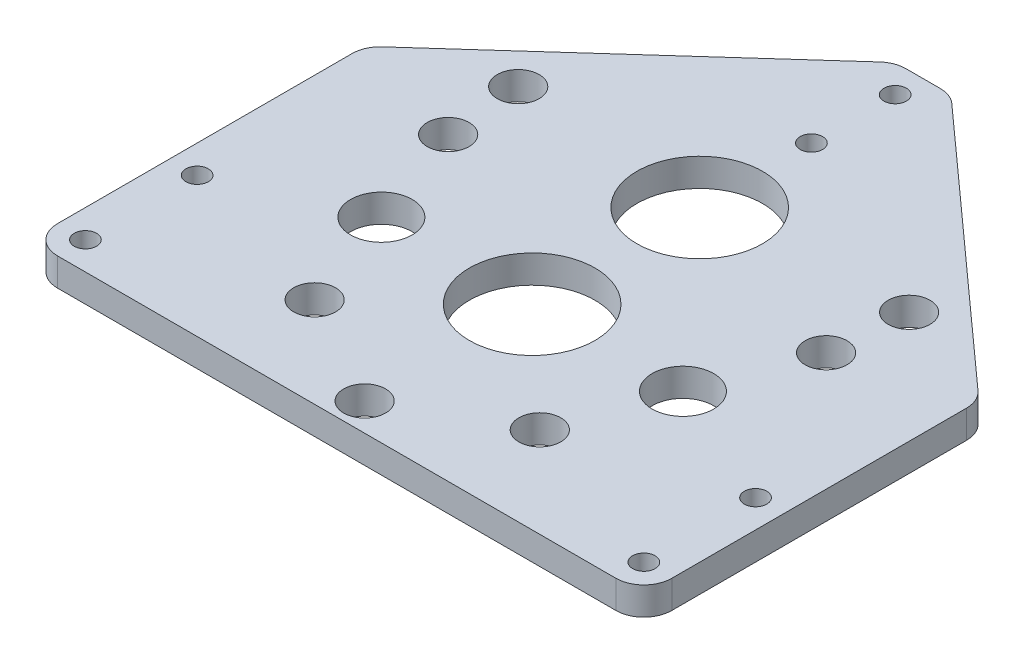
SolidWorks part; units mm, degrees
material "6061-T6 (SS)"
ref_plane "Front Plane" through (0, 0, 0) normal (0, 0, 1) x (1, 0, 0)
ref_plane "Top Plane" through (0, 0, 0) normal (0, 1, 0) x (1, 0, 0)
ref_plane "Right Plane" through (0, 0, 0) normal (1, 0, 0) x (0, 0, -1)
sketch "Sketch1" plane through (0, 0, 0) normal (0, 1, 0) x (1, 0, 0)
  line L0 (-69.85, -19.05) -> (69.85, -19.05)
  line L1 (69.85, -19.05) -> (69.85, 57.15)
  line L2 (69.85, 57.15) -> (6.35, 114.3)
  line L3 (6.35, 114.3) -> (-6.35, 114.3)
  line L4 (-6.35, 114.3) -> (-69.85, 57.15)
  line L5 (-69.85, 57.15) -> (-69.85, -19.05)
  line L6 (0, 0) -> (0, -19.05) construction
  dimension "D1" = 139.7
  dimension "D2" = 12.7
  dimension "D3" = 114.3
  dimension "D4" = 19.05
  dimension "D5" = 57.15
extrude "Boss-Extrude1" add sketch "Sketch1" along normal blind 6.35
sketch "Sketch2" plane through (0, 6.35, 0) normal (0, 1, 0) x (1, 0, 0)
  line L0 (-34.29, 25.4) -> (0, -19.05) construction
  line L1 (-69.85, -19.05) -> (69.85, -19.05) construction
  line L2 (0, -19.05) -> (34.29, 25.4) construction
  circle A0 centre (-34.29, 25.4) radius 7
  circle A1 centre (34.29, 25.4) radius 7
  dimension "D1" = 14
  dimension "D2" = 68.58
  dimension "D3" = 25.4
extrude "Motor Bearing Holes" cut sketch "Sketch2" against normal through all
sketch "Sketch3" plane through (0, 6.35, 0) normal (0, 1, 0) x (1, 0, 0)
  line L0 (-34.29, 25.4) -> (34.29, 25.4) construction
  circle A0 centre (0, 25.4) radius 14.2875
  dimension "D1" = 28.575
extrude "Cut-Extrude1" cut sketch "Sketch3" against normal through all
sketch "Sketch4" plane through (0, 6.35, 0) normal (0, 1, 0) x (1, 0, 0)
  circle A0 centre (0, 63.5) radius 14.2875
  circle A1 centre (0, 25.4) radius 14.2875 construction
  dimension "D1" = 28.575
  dimension "D2" = 38.1
extrude "Cut-Extrude2" cut sketch "Sketch4" against normal through all
extrude "Cut-Extrude3" cut sketch "Sketch5" against normal blind 50.8
sketch "Sketch5" plane through (0, 38.1, 19.05) normal (0, 1, 0) x (-0.9584, 0, 0.2853)
  circle A0 centre (21.6972, -77.741) radius 4.7625
  circle A1 centre (18.6656, -27.0315) radius 4.7625
  circle A2 centre (-30.411, -12.4209) radius 4.7625
  circle A3 centre (-60.6842, -53.2152) radius 4.7625
hole_wizard "#10 Clearance Hole1" positions "Sketch6" profile "Sketch7" hole size "#10" standard "ANSI Inch" end condition through all
sketch "Sketch6" plane through (0, 6.35, 19.05) normal (0, 1, 0) x (1, 0, 0)
  point P0 (-63.5, 6.35)
  point P2 (63.5, 6.35)
  point P13 (0, 107.95)
sketch "Sketch7" plane through (-63.5, 6.35, 12.7) normal (1, 0, 0) x (0, 0, 1)
  line L0 (0, 0) -> (0, 6.35)
  line L1 (0, 6.35) -> (2.5527, 6.35)
  line L2 (2.5527, 6.35) -> (2.5527, 0)
  line L3 (2.5527, 0) -> (0, 0)
  line L4 (0, -6.35) -> (0, 107.95) construction
  dimension "Thru Hole Dia." = 5.1054
  dimension "Thru Hole Depth" = 6.35
hole_wizard "#10 Clearance Hole2" positions "Sketch8" profile "Sketch9" hole size "#10" standard "ANSI Inch"
sketch "Sketch8" plane through (0, 38.1, 19.05) normal (0, 1, 0) x (1, 0, 0)
  point P0 (-63.5, 31.75)
  point P2 (63.5, 31.75)
  point P4 (0, 127)
sketch "Sketch9" plane through (-63.5, 38.1, -12.7) normal (1, 0, 0) x (0, 0, 1)
  line L0 (0, 0) -> (0, 52.3338)
  line L1 (0, 52.3338) -> (2.5527, 50.8)
  line L2 (2.5527, 50.8) -> (2.5527, 0)
  line L3 (2.5527, 0) -> (0, 0)
  line L4 (0, 52.3338) -> (-2.5527, 50.8) construction
  line L5 (0, -6.35) -> (0, 107.95) construction
  dimension "Hole Dia." = 5.1054
  dimension "Hole Depth" = 50.8
  dimension "Drill Angle" = 118
fillet "Fillet1" radius 6.35 6 edges at (-6.35, 3.175, -114.3) (6.35, 3.175, -114.3) (69.85, 3.175, -57.15) (69.85, 3.175, 19.05) (-69.85, 3.175, -57.15) (-69.85, 3.175, 19.05)
extrude "Cut-Extrude4" cut sketch "Sketch10" against normal blind 50.8
sketch "Sketch10" plane through (0, -28.575, 19.05) normal (0, -1, 0) x (-1, 0, 0)
  circle A0 centre (-44.45, 85.725) radius 4.7625
  circle A1 centre (44.45, 85.725) radius 4.7625
  circle A2 centre (0, 6.35) radius 4.7625
